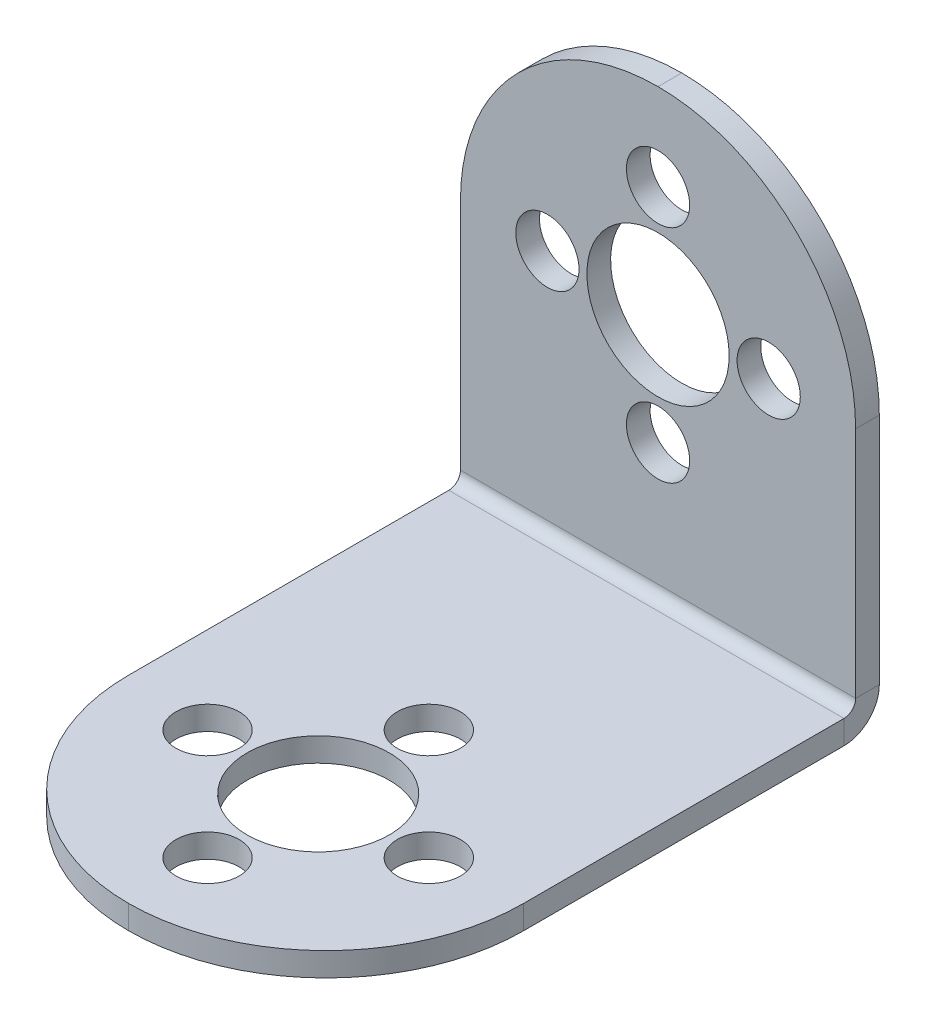
SolidWorks part; units mm, degrees
note: The reader was unsure of these and kept them because the rebuilt part matched: flange length of "Edge-Flange1".
ref_plane "Front Plane" through (0, 0, 0) normal (0, 0, 1) x (1, 0, 0)
ref_plane "Top Plane" through (0, 0, 0) normal (0, 1, 0) x (1, 0, 0)
ref_plane "Right Plane" through (0, 0, 0) normal (1, 0, 0) x (0, 0, -1)
sketch "Sketch1" plane through (0, 0, 0) normal (0, 1, 0) x (1, 0, 0)
  line L0 (0, 17.5) -> (0, -17.5) construction
  line L1 (-12.5, 17.5) -> (12.5, 17.5)
  line L2 (-12.5, 17.5) -> (-12.5, -17.5)
  line L3 (-12.5, -17.5) -> (12.5, -17.5)
  line L4 (12.5, 17.5) -> (12.5, -17.5)
  line L5 (-12.5, 17.5) -> (12.5, -17.5) construction
  line L6 (-12.5, -17.5) -> (12.5, 17.5) construction
  circle A5 centre (0, -5.5) radius 4.5
  circle A6 centre (-7, -5.5) radius 2
  circle A7 centre (0, -12.5) radius 2
  circle A8 centre (7, -5.5) radius 2
  circle A9 centre (0, 1.5) radius 2
  point P0 (0, 0)
  point P18 (0, -5.3436)
  point P19 (-7, -5.5)
  point P20 (7, -5.5)
  dimension "D3" = 9
  dimension "D4" = 4
  dimension "D1" = 25
  dimension "D2" = 35
  dimension "D5" = 12
  dimension "D6" = 7
  dimension "D7" = 7
  dimension "D8" = 7
  dimension "D9" = 7
base flange "Base-Flange1" sketch "Sketch1" thickness 1.5 reverse thickness direction yes parameters "D1"=0.7366
edge flange "Edge-Flange1" sketch "Sketch8" flange angle 90 flange length 28 flange position material inside bend radius 0.7366 thickness 1.5 relief rectangular parameters "D6"=10
sketch "Sketch8" plane through (0, 1.5, -17.5) normal (0, 0, -1) x (-1, 0, 0)
  line L0 (-12.5, 0) -> (12.5, 0) construction
  line L1 (-12.5, 0) -> (12.5, 0)
  line L2 (-12.5, 0) -> (-12.5, 28)
  line L3 (-12.5, 28) -> (12.5, 28)
  line L4 (12.5, 28) -> (12.5, 0)
bend "EdgeBend1" bend radius 0.7366 bend angle 90 parameters "D5"=1
sketch "Sketch9" plane through (0, 0, -16) normal (0, 0, 1) x (1, 0, 0)
  line L0 (-12.5, 29.5) -> (12.5, 29.5) construction
  circle A0 centre (0, 17) radius 4.5
  circle A1 centre (-7, 17) radius 2
  circle A2 centre (7, 17) radius 2
  circle A3 centre (0, 24) radius 2
  circle A4 centre (0, 10) radius 2
  point P10 (0, 23.5)
  point P11 (0, 23.5)
  point P12 (0, 0)
  point P13 (0, 23.5)
  point P14 (0, 19.577)
  dimension "D1" = 9
  dimension "D2" = 4
  dimension "D3" = 7
  dimension "D4" = 7
  dimension "D5" = 7
  dimension "D6" = 7
  dimension "D7" = 5.5
extrude "Cut-Extrude1" cut sketch "Sketch9" against normal blind 10 normal cut yes
fillet "Fillet1" radius 12.5 4 edges at (12.5, 0.75, 17.5) (-12.5, 0.75, 17.5) (12.5, 29.5, -16.75) (-12.5, 29.5, -16.75)
sketch "Bend-Lines1" [suppressed] plane through (0, 0, 0) normal (0, 1, 0) x (1, 0, 0)
sketch "Bounding-Box1" [suppressed] plane through (0, 0, 0) normal (0, 1, 0) x (1, 0, 0)
sheet metal parameters "Sheet-Metal1" thickness 1.5 parameters "D1"=0.7366
flat pattern "Flat-Pattern1" [suppressed]
sketch "Bend-Lines2" plane through (0, 0, 0) normal (0, 1, 0) x (1, 0, 0)
sketch3d "Bounding-Box2" [suppressed]
  line L0 (-6, 8, 0) -> (-6, -8, 0) construction
  line L1 (6, 8, 0) -> (6, -8, 0) construction
  line L2 (-6, 8, 0) -> (6, 8, 0) construction
  line L3 (-6, -8, 0) -> (6, -8, 0) construction
sheet metal parameters "Sheet-Metal2" thickness 1.5 parameters "D1"=0.7366
flat pattern "Flat-Pattern1"
sketch "Bend-Lines2" plane through (0, 0, 0) normal (0, -1, 0) x (-1, 0, 0)
  line L0 (6, 6.931) -> (-6, 6.931) construction
  line L1 (6, 6.931) -> (-6, 6.931) construction
sketch3d "Bounding-Box2" [suppressed]
  line L0 (6, 21.3619, 0) -> (6, -8, 0) construction
  line L1 (-6, 21.3619, 0) -> (-6, -8, 0) construction
  line L2 (6, 21.3619, 0) -> (-6, 21.3619, 0) construction
  line L3 (6, -8, 0) -> (-6, -8, 0) construction
bend of the flat pattern "Flatten-<EdgeBend1>1"
sheet metal parameters "Sheet-Metal3" thickness 1.5 parameters "D1"=0.7366
flat pattern "Flat-Pattern1"
sketch "Bend-Lines2" plane through (0, 0, 0) normal (0, -1, 0) x (-1, 0, 0)
  line L0 (12.5, 16.431) -> (-12.5, 16.431) construction
  line L1 (12.5, 16.431) -> (-12.5, 16.431) construction
sketch3d "Bounding-Box2" [suppressed]
  line L0 (12.5, 44.8619, 0) -> (12.5, -17.5, 0) construction
  line L1 (-12.5, 44.8619, 0) -> (-12.5, -17.5, 0) construction
  line L2 (12.5, 44.8619, 0) -> (-12.5, 44.8619, 0) construction
  line L3 (12.5, -17.5, 0) -> (-12.5, -17.5, 0) construction
bend of the flat pattern "Flatten-<EdgeBend1>1"
